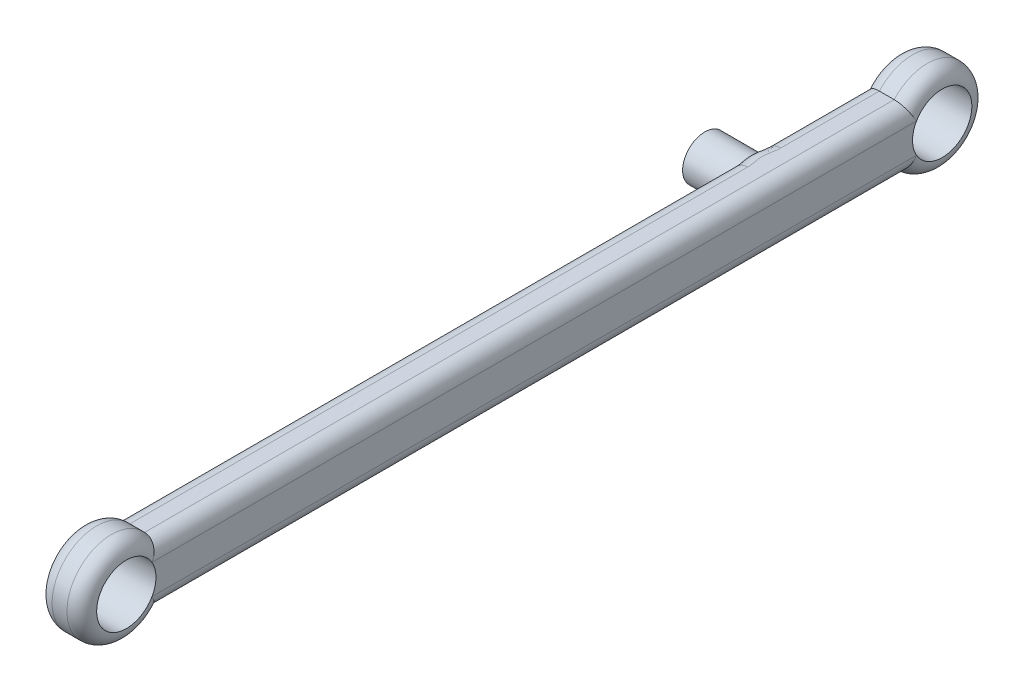
SolidWorks part; units mm, degrees
ref_plane "Front Plane" through (0, 0, 0) normal (0, 0, 1) x (1, 0, 0)
ref_plane "Top Plane" through (0, 0, 0) normal (0, 1, 0) x (1, 0, 0)
ref_plane "Right Plane" through (0, 0, 0) normal (1, 0, 0) x (0, 0, -1)
sketch "Sketch1" plane through (0, 0, 0) normal (1, 0, 0) x (0, 0, -1)
  line L2 (-2.2361, -2) -> (-52.7639, -2)
  line L3 (-2.2361, 2) -> (-52.7639, 2)
  arc A2 (-52.7639, 2) -> (-52.7639, -2) centre (-55, 0) ccw
  arc A3 (-2.2361, -2) -> (-2.2361, 2) centre (0, 0) ccw
  point P3 (-27.5, 0)
extrude "Boss-Extrude1" add sketch "Sketch1" along normal blind 3
sketch "Sketch2" plane through (0, 0, 0) normal (1, 0, 0) x (0, 0, -1)
  circle A0 centre (-55, 0) radius 2
  circle A1 centre (0, 0) radius 2
  dimension "D1" = 4
  dimension "D2" = 4
extrude "Cut-Extrude1" cut sketch "Sketch2" along normal blind 3
sketch "Sketch3" plane through (3, 0, 0) normal (1, 0, 0) x (0, 0, -1)
  line L0 (-50.1677, 0) -> (-5.1677, 0) construction
  line L2 (-50.1677, 1) -> (-5.1677, 1)
  line L3 (-50.1677, -1) -> (-5.1677, -1)
  arc A0 (-50.1677, 1) -> (-50.1677, -1) centre (-50.1677, 0) ccw
  arc A1 (-5.1677, -1) -> (-5.1677, 1) centre (-5.1677, 0) ccw
  point P0 (-27.6677, 0)
  point P7 (-27.6677, 0)
extrude "Cut-Extrude2" [suppressed] cut sketch "Sketch3" against normal blind 3
sketch "Sketch4" plane through (3, 0, 0) normal (1, 0, 0) x (0, 0, -1)
  line L0 (-55, 0) -> (-10, 0) construction
  circle A0 centre (-10, 0) radius 1.5
  dimension "D1" = 3
  dimension "D2" = 45
extrude "Boss-Extrude2" add sketch "Sketch4" against normal blind 6 contours A0
fillet "Fillet1" radius 1 8 edges at (3, 2, 27.5) (3, -2, 27.5) (3, 0, 58) (3, 0, -3) (0, 0, 58) (0, 0, -3) (0, -2, 27.5) (0, 2, 27.5)
scale "Scale1" scale about origin uniform scaling yes scale factor 1.5
